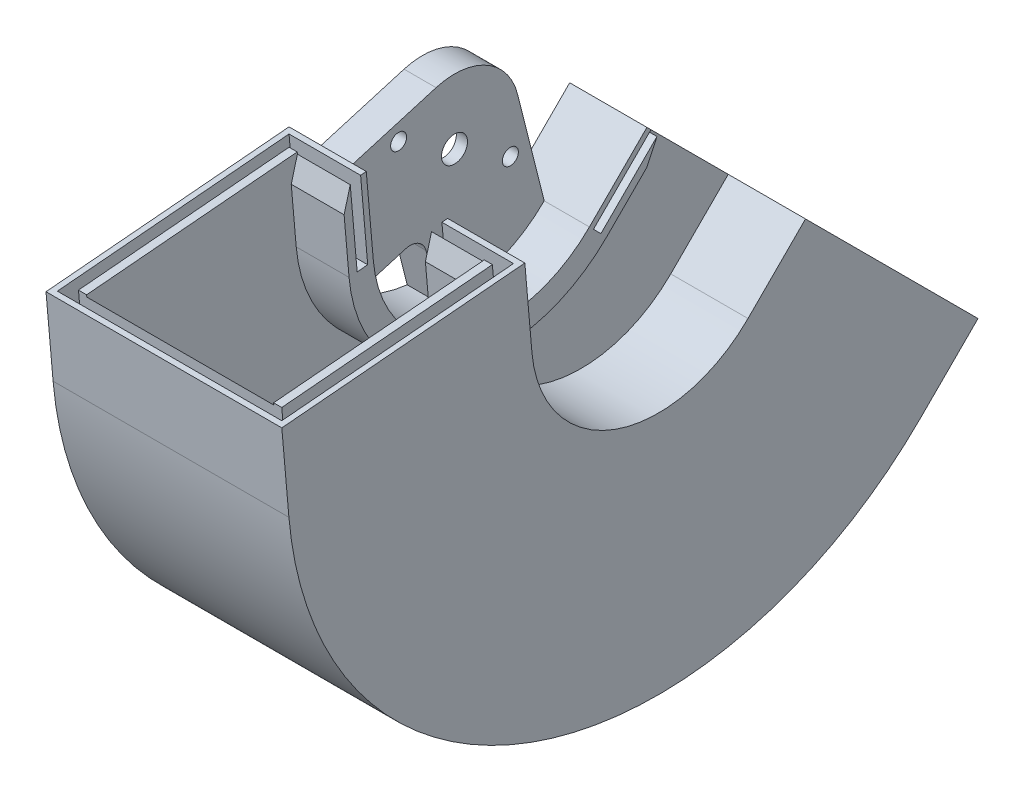
SolidWorks part; units mm, degrees
ref_plane "Front Plane" through (0, 0, 0) normal (0, 0, 1) x (1, 0, 0)
ref_plane "Top Plane" through (0, 0, 0) normal (0, 1, 0) x (1, 0, 0)
ref_plane "Right Plane" through (0, 0, 0) normal (1, 0, 0) x (0, 0, -1)
sketch "Sketch3" plane through (0, 0, 0) normal (1, 0, 0) x (0, 0, -1)
  line L0 (-39.4732, -3.4535) -> (-107.7923, -9.4306)
  line L1 (28.0184, -28.0184) -> (76.5118, -76.5118)
  line L2 (-39.4732, -3.4535) -> (0, 0) construction
  line L3 (0, 0) -> (28.0184, -28.0184) construction
  line L4 (0, 55) -> (0, -55) construction
  line L5 (-107.7923, -9.4306) -> (-115.3833, -10.0947)
  line L6 (76.5118, -76.5118) -> (81.8999, -81.8999)
  arc A2 (-107.7923, -9.4306) -> (76.5118, -76.5118) centre (0, 0) ccw
  arc A4 (-47.0642, -4.1176) -> (33.4066, -33.4066) centre (0, 0) ccw
  arc A5 (-39.4732, -3.4535) -> (28.0184, -28.0184) centre (0, 0) ccw
  arc A6 (-115.3833, -10.0947) -> (81.8999, -81.8999) centre (0, 0) ccw
  dimension "D1" = 216.408
  dimension "D2" = 135
  dimension "D3" = 94.488
  dimension "D4" = 7.62
  dimension "D6" = 7.62
  dimension "D5" = 130
extrude "Boss-Extrude2" add sketch "Sketch3" along normal blind 58.42 contours L5 A6 L6 A2 | A5 L0 A4 L1 region at (0, -38.0953, 13.8655) region at (0, -103.7848, 37.7746)
sketch "Sketch4" plane through (58.42, 0, 0) normal (1, 0, 0) x (0, 0, -1)
  line L0 (-115.3833, -10.0947) -> (-39.4732, -3.4535)
  line L1 (28.0184, -28.0184) -> (81.8999, -81.8999)
  arc A0 (-39.4732, -3.4535) -> (28.0184, -28.0184) centre (0, 0) ccw
  arc A1 (-39.4732, -3.4535) -> (28.0184, -28.0184) centre (0, 0) ccw construction
  arc A2 (-115.3833, -10.0947) -> (81.8999, -81.8999) centre (0, 0) ccw
  arc A3 (-115.3833, -10.0947) -> (81.8999, -81.8999) centre (0, 0) ccw construction
  arc M1 (28.0184, -28.0184) -> (-39.4732, -3.4535) centre (0, 0) cw
  line M2 (-39.4732, -3.4535) -> (-47.0642, -4.1176)
  arc M3 (-47.0642, -4.1176) -> (33.4066, -33.4066) centre (0, 0) ccw
  line M4 (33.4066, -33.4066) -> (28.0184, -28.0184)
extrude "Boss-Extrude3" add sketch "Sketch4" along normal blind 7.62 contours L0 A2 L1 M3 | M4 M1 M2 M3 region at (58.42, -64.8169, 23.5914) region at (58.42, -4.6982, 43.1889)
ref_plane "Midplane" through (29.21, 0, 0) normal (-1, 0, 0) x (0, 0, 1)
mirror "Mirror1" about plane through (29.21, 0, 0) normal (-1, 0, 0) of "Boss-Extrude3"
sketch "Sketch6" plane through (0, 0, 0) normal (0, 0.9962, 0.0872) x (1, 0, 0)
  line L27 (-5.842, -41.402) -> (64.262, -41.402)
  line L28 (-5.842, -41.402) -> (-5.842, -114.046)
  line L29 (-5.842, -114.046) -> (64.262, -114.046)
  line L30 (64.262, -41.402) -> (64.262, -114.046)
  line L31 (-2.54, -44.704) -> (60.96, -44.704)
  line L32 (-2.54, -44.704) -> (-2.54, -110.744)
  line L33 (-2.54, -110.744) -> (60.96, -110.744)
  line L34 (60.96, -44.704) -> (60.96, -110.744)
  line L35 (58.42, -47.244) -> (0, -47.244) construction
  line L36 (0, -108.204) -> (0, 69.5522) construction
  line L37 (58.42, 69.5522) -> (58.42, -108.204) construction
  line L38 (58.42, -108.204) -> (0, -108.204) construction
  line L40 (0, -47.244) -> (58.42, -47.244)
  line L41 (0, -47.244) -> (0, -108.204)
  line L42 (0, -108.204) -> (58.42, -108.204)
  line L43 (58.42, -47.244) -> (58.42, -108.204)
  line L44 (-7.62, -39.624) -> (66.04, -39.624)
  line L45 (-7.62, -39.624) -> (-7.62, -115.824)
  line L46 (-7.62, -115.824) -> (66.04, -115.824)
  line L47 (66.04, -39.624) -> (66.04, -115.824)
  line M21 (-7.62, -39.624) -> (-7.62, -115.824)
  line M22 (-7.62, -115.824) -> (66.04, -115.824)
  line M23 (66.04, -115.824) -> (66.04, -39.624)
  line M24 (66.04, -39.624) -> (-7.62, -39.624)
  line M25 (58.42, -108.204) -> (0, -108.204)
  line M26 (0, -108.204) -> (0, -47.244)
  line M27 (0, -47.244) -> (58.42, -47.244)
  line M28 (58.42, -47.244) -> (58.42, -108.204)
  dimension "D1" = 3.302
  dimension "D2" = 3.302
  dimension "D3" = 3.302
  dimension "D4" = 3.302
  dimension "D5" = 2.54
  dimension "D6" = 2.54
  dimension "D7" = 2.54
  dimension "D8" = 2.54
extrude "Boss-Extrude4" add sketch "Sketch6" along normal blind 25.4 contours L27 L30 L29 L28 M24 M21 M22 M23 | L34 L31 L32 L33 M28 M25 M26 M27 region at (29.21, -3.9761, 45.4466) region at (29.21, -3.5458, 40.529)
sketch "Sketch7" plane through (0, 0, 0) normal (0, 0.7071, -0.7071) x (1, 0, 0)
  line L0 (-5.842, 114.046) -> (64.262, 114.046)
  line L1 (-5.842, 114.046) -> (-5.842, 41.402)
  line L2 (-5.842, 41.402) -> (64.262, 41.402)
  line L3 (64.262, 114.046) -> (64.262, 41.402)
  line L4 (-2.54, 110.744) -> (60.96, 110.744)
  line L5 (-2.54, 110.744) -> (-2.54, 44.704)
  line L6 (-2.54, 44.704) -> (60.96, 44.704)
  line L7 (60.96, 110.744) -> (60.96, 44.704)
  line L8 (0, 108.204) -> (58.42, 108.204)
  line L9 (0, 108.204) -> (0, 47.244)
  line L10 (0, 47.244) -> (58.42, 47.244)
  line L11 (58.42, 108.204) -> (58.42, 47.244)
  line L12 (-7.62, 115.824) -> (66.04, 115.824)
  line L13 (-7.62, 115.824) -> (-7.62, 39.624)
  line L14 (-7.62, 39.624) -> (66.04, 39.624)
  line L15 (66.04, 115.824) -> (66.04, 39.624)
  line L16 (58.42, 108.204) -> (0, 108.204) construction
  line L17 (58.42, 47.244) -> (58.42, 108.204) construction
  line L18 (66.04, 115.824) -> (-7.62, 115.824) construction
  line L19 (66.04, 39.624) -> (66.04, 115.824) construction
  line L20 (-7.62, 39.624) -> (-7.62, 115.824) construction
  line L21 (66.04, 39.624) -> (-7.62, 39.624) construction
  line M17 (66.04, 115.824) -> (-7.62, 115.824)
  line M18 (-7.62, 115.824) -> (-7.62, 39.624)
  line M19 (-7.62, 39.624) -> (66.04, 39.624)
  line M20 (66.04, 39.624) -> (66.04, 115.824)
  line M21 (0, 47.244) -> (0, 108.204)
  line M22 (0, 108.204) -> (58.42, 108.204)
  line M23 (58.42, 108.204) -> (58.42, 47.244)
  line M24 (58.42, 47.244) -> (0, 47.244)
  dimension "D1" = 3.302
  dimension "D2" = 3.302
  dimension "D3" = 3.302
  dimension "D4" = 3.302
  dimension "D5" = 2.54
  dimension "D6" = 2.54
  dimension "D7" = 2.54
  dimension "D8" = 2.54
extrude "Boss-Extrude5" add sketch "Sketch7" along normal blind 25.4 contours L0 L3 L2 L1 M20 M17 M18 M19 | L7 L4 L5 L6 M24 M21 M22 M23 region at (29.21, -77.66, -77.66) region at (29.21, -81.1505, -81.1505)
chamfer "Chamfer1" distance 7.62 angle 20 4 edges at (29.21, 15.8727, 110.006) (29.21, 21.1858, 49.278) (29.21, -58.5513, -94.4723) (29.21, -15.446, -51.3671) first distance on face at (29.21, 3.2211, 108.8991) first distance on face at (29.21, 8.5341, 48.1711) first distance on face at (29.21, -67.5315, -85.492) first distance on face at (29.21, -24.4263, -42.3868)
ref_plane "Plane2" through (0, 5.896, -2.146) normal (0, -0.9397, 0.342) x (-1, 0, 0)
sketch "Sketch10" plane through (0, 5.896, -2.146) normal (0, -0.9397, 0.342) x (-1, 0, 0)
  line L0 (-66.04, 115.7067) -> (7.62, 115.7067) construction
  line L1 (-16.51, 95.5358) -> (-41.91, 95.5358)
  line L2 (-16.51, 95.5358) -> (-16.51, -82.1857)
  line L3 (-16.51, -82.1857) -> (-41.91, -82.1857)
  line L4 (-41.91, 95.5358) -> (-41.91, -82.1857)
  point P4 (-29.21, 115.7067)
  point P5 (-29.21, 95.5358)
  dimension "D1" = 25.4
extrude "Cut-Extrude3" cut sketch "Sketch10" along normal up to next
sketch "Sketch11" plane through (-7.62, 0, 0) normal (-1, 0, 0) x (0, 0, 1)
  line L0 (-19.7036, 4.9668) -> (-28.0184, -28.0184)
  line L4 (8.8954, -22.9941) -> (4.7763, -39.3351)
  line L5 (15.2608, -19.364) -> (31.4223, -24.1392)
  line L6 (-17.454, -10.7521) -> (17.454, 10.7521) construction
  line L7 (5.7579, 19.4872) -> (40.5801, 9.1982)
  line L8 (41.687, 21.8499) -> (39.4732, -3.4535) construction
  line L10 (11.3048, -19.823) -> (-10.0663, 17.6514) construction
  line L11 (39.4732, -3.4535) -> (41.687, 21.8499)
  line L12 (39.4732, -3.4535) -> (40.5801, 9.1982)
  arc A1 (-28.0184, -28.0184) -> (39.4732, -3.4535) centre (0, 0) ccw construction
  circle A3 centre (0, 0) radius 4.064
  arc A4 (5.7579, 19.4872) -> (-19.7036, 4.9668) centre (0, 0) ccw
  circle A6 centre (-17.454, -10.7521) radius 2.5
  circle A7 centre (17.454, 10.7521) radius 2.5
  arc A8 (8.8954, -22.9941) -> (15.2608, -19.364) centre (13.8213, -24.2358) cw
  arc A11 (31.4223, -24.1392) -> (39.4732, -3.4535) centre (0, 0) ccw
  arc A12 (-28.0184, -28.0184) -> (39.4732, -3.4535) centre (0, 0) ccw
  arc A13 (-28.0184, -28.0184) -> (4.7763, -39.3351) centre (0, 0) ccw
  point P8 (13.8213, -24.1392)
  point P22 (0, 0)
  dimension "D3" = 8.128
  dimension "D2" = 20.32
  dimension "D1" = 5
  dimension "D5" = 5.08
  dimension "D4" = 41
  dimension "D6" = 0
extrude "Boss-Extrude6" add sketch "Sketch11" against normal blind 10
sketch "Sketch12" plane through (-7.62, 0, 0) normal (-1, 0, 0) x (0, 0, 1)
  circle A0 centre (0, 0) radius 17
  dimension "D1" = 34
extrude "Cut-Extrude4" cut sketch "Sketch12" against normal blind 6.5
